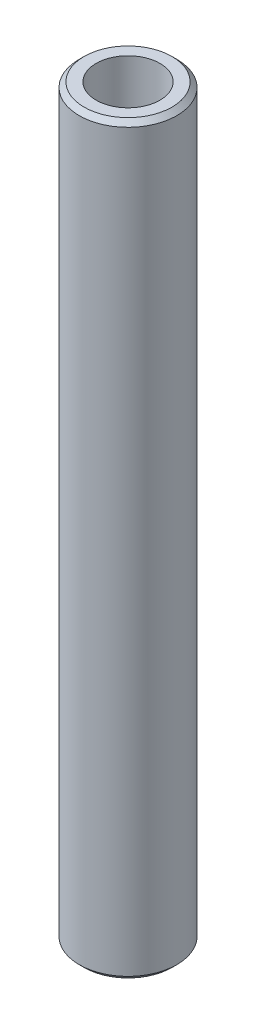
SolidWorks part; units mm, degrees
ref_plane "Front Plane" through (0, 0, 0) normal (0, 0, 1) x (1, 0, 0)
ref_plane "Top Plane" through (0, 0, 0) normal (0, 1, 0) x (1, 0, 0)
ref_plane "Right Plane" through (0, 0, 0) normal (1, 0, 0) x (0, 0, -1)
sketch "Sketch1" plane through (0, 0, 0) normal (0, 1, 0) x (1, 0, 0)
  circle A0 centre (0, 0) radius 22.5
  dimension "SHAFT_OD" = 45
extrude "Boss-Extrude1" add sketch "Sketch1" along normal blind 343.3567
sketch "Sketch2" plane through (0, 0, 0) normal (0, 1, 0) x (1, 0, 0)
  circle A0 centre (0, 0) radius 14.7062
  dimension "BORE_D" = 29.4124
extrude "Cut-Extrude1" cut sketch "Sketch2" along normal through all
chamfer "Chamfer1" distance 2.2625 angle 45 2 edges at (0, 343.3567, 22.5) (0, 0, 22.5)
